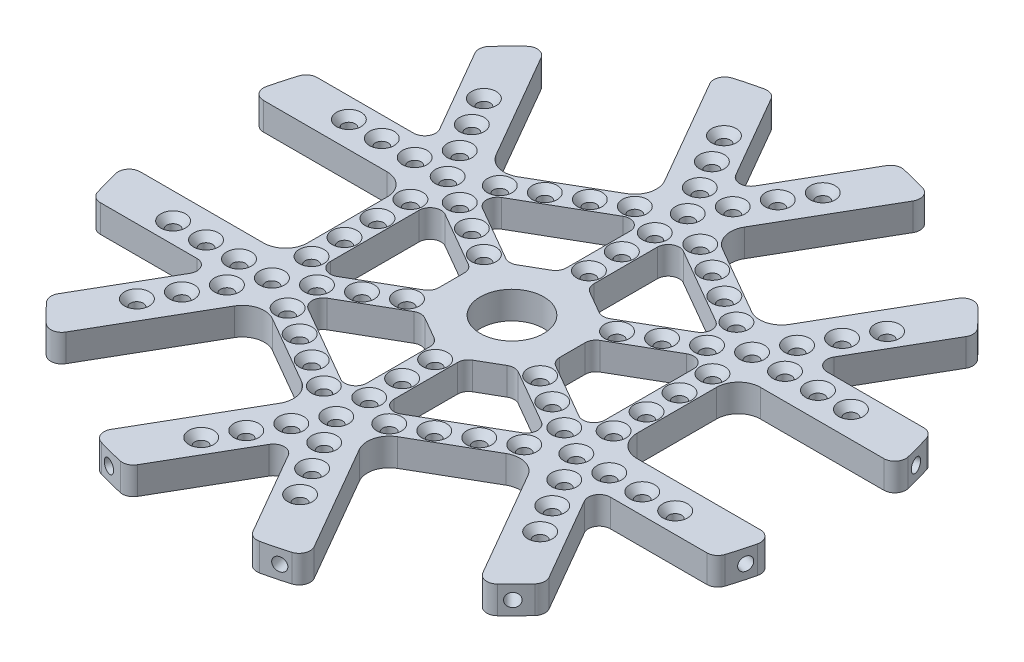
SolidWorks part; units mm, degrees
material "6061-T6 (SS)"
ref_plane "Front Plane" through (0, 0, 0) normal (0, 0, 1) x (1, 0, 0)
ref_plane "Top Plane" through (0, 0, 0) normal (0, 1, 0) x (1, 0, 0)
ref_plane "Right Plane" through (0, 0, 0) normal (1, 0, 0) x (0, 0, -1)
sketch "Sketch1" plane through (0, 0, 0) normal (0, 1, 0) x (1, 0, 0)
  line L0 (0, -76.2) -> (0, 94.2288) construction
  line L1 (0, 0) -> (-65.9911, 38.1) construction
  line L2 (0, 0) -> (-19.722, 73.6035) construction
  line L3 (-14.2714, 74.8516) -> (0, 50.1328)
  line L4 (-25.0664, 71.9591) -> (0, 28.5428)
  line L5 (0, 50.1328) -> (0, 34.0421)
  line L6 (0, 0) -> (-3.175, 0)
  line L7 (0, 0) -> (0, 34.0421)
  line L8 (0, 34.0421) -> (-3.175, 34.0421)
  line L9 (-3.175, 0) -> (-3.175, 34.0421)
  arc A1 (-25.0664, 71.9591) -> (-19.722, 73.6035) centre (0, 0) cw
  arc A3 (-14.2714, 74.8516) -> (-19.722, 73.6035) centre (0, 0) ccw
  circle A4 centre (0, 0) radius 76.2
  dimension "D6" = 152.4
  dimension "D7" = 76.2
  dimension "D8" = 76.2
  dimension "D1" = 15
  dimension "D2" = 60
  dimension "D3" = 30
  dimension "D4" = 10.795
  dimension "D5" = 3.175
extrude "Boss-Extrude1" add sketch "Sketch1" along normal blind 6.35 contours L3 A3 A1 L4 L8 L5
mirror "Mirror1" of "Boss-Extrude1"
sketch "Sketch2" plane through (0, 0, 0) normal (0, 0, 1) x (1, 0, 0)
  line L0 (0, 6.35) -> (0, 0)
  line L1 (3.175, 6.35) -> (-3.175, 6.35) construction
pattern_circular "CirPattern9" count 6 over 360 about axis through (0, 0, 0) along (0, 1, 0) of bodies 102
ref_plane "Plane1" through (3.175, 6.35, 0) normal (0, 0, -1) x (-1, 0, 0)
sketch "Sketch4" plane through (0, 6.35, 0) normal (0, 1, 0) x (1, 0, 0)
  line L1 (0, 16.1312) -> (-13.97, 8.0656)
  line L2 (-13.97, 8.0656) -> (-13.97, -8.0656)
  line L3 (-13.97, -8.0656) -> (0, -16.1312)
  line L4 (0, -16.1312) -> (13.97, -8.0656)
  line L5 (13.97, -8.0656) -> (13.97, 8.0656)
  line L6 (13.97, 8.0656) -> (0, 16.1312)
  circle A0 centre (0, 0) radius 13.97 construction
  dimension "D1" = 27.94
extrude "Boss-Extrude2" add sketch "Sketch4" against normal blind 6.35
sketch "Sketch5" plane through (0, 6.35, 0) normal (0, 1, 0) x (1, 0, 0)
  circle A0 centre (0, 0) radius 6.35
extrude "Cut-Extrude1" cut sketch "Sketch5" against normal blind 6.35
sketch "Sketch6" plane through (0, 6.35, 0) normal (0, 1, 0) x (1, 0, 0)
  line L0 (-28.7945, 20.0372) -> (-2.9555, 34.9554)
  line L1 (-28.7945, 20.0372) -> (-31.9695, 25.5365)
  line L2 (-2.9555, 34.9554) -> (-6.1305, 40.4547)
  line L3 (-31.9695, 25.5365) -> (-6.1305, 40.4547)
  point P0 (-15.875, 27.4963)
  dimension "D1" = 6.35
  dimension "D2" = 31.75
extrude "Boss-Extrude3" add sketch "Sketch6" against normal blind 6.35
pattern_circular "CirPattern10" count 6 every 60 about axis through (0, 0, 0) along (0, 1, 0) of "Boss-Extrude3"
ref_plane "Plane4" through (0, 3.175, 0) normal (0, 1, 0) x (1, 0, 0)
extrude "Cut-Extrude3" cut sketch "Sketch46" against normal blind 7.62
sketch "Sketch46" plane through (0, 6.35, 0) normal (0, 1, 0) x (1, 0, 0)
  line L0 (3.175, -34.8287) -> (3.5156, -34.632)
  line L2 (3.5156, -34.632) -> (3.175, -34.0421)
  line L4 (3.5156, -34.632) -> (3.175, -34.0421)
  line L5 (3.5156, -34.632) -> (3.175, -34.0421) construction
  line L6 (3.175, -34.0421) -> (3.175, -34.8287)
  line L7 (3.175, -34.0421) -> (3.5156, -34.632)
  line L8 (0, -3.4925) -> (0, 3.4925) construction
  line L9 (-3.5156, -34.632) -> (-3.175, -34.0421)
  line L10 (-3.175, -34.8287) -> (-3.5156, -34.632)
  line L11 (-3.175, -34.0421) -> (-3.175, -34.8287)
  line L12 (-31.0688, -14.2714) -> (-31.75, -14.6647)
  line L13 (-31.75, -14.2714) -> (-31.0688, -14.2714)
  line L14 (-31.75, -14.6647) -> (-31.75, -14.2714)
  line L15 (-28.2344, -20.3606) -> (-27.8938, -19.7707)
  line L16 (-27.8938, -19.7707) -> (-28.575, -20.164)
  line L17 (-28.575, -20.164) -> (-28.2344, -20.3606)
  line L18 (-27.8938, 19.7707) -> (-28.575, 20.164)
  line L19 (-28.2344, 20.3606) -> (-27.8938, 19.7707)
  line L20 (-28.575, 20.164) -> (-28.2344, 20.3606)
  line L21 (-31.75, 14.2714) -> (-31.0688, 14.2714)
  line L22 (-31.0688, 14.2714) -> (-31.75, 14.6647)
  line L23 (-31.75, 14.6647) -> (-31.75, 14.2714)
  line L24 (3.175, 34.0421) -> (3.175, 34.8287)
  line L25 (3.5156, 34.632) -> (3.175, 34.0421)
  line L26 (3.175, 34.8287) -> (3.5156, 34.632)
  line L27 (-3.5156, 34.632) -> (-3.175, 34.0421)
  line L28 (-3.175, 34.0421) -> (-3.175, 34.8287)
  line L29 (-3.175, 34.8287) -> (-3.5156, 34.632)
  line L30 (31.0688, 14.2714) -> (31.75, 14.6647)
  line L31 (31.75, 14.2714) -> (31.0688, 14.2714)
  line L32 (31.75, 14.6647) -> (31.75, 14.2714)
  line L33 (28.2344, 20.3606) -> (27.8938, 19.7707)
  line L34 (27.8938, 19.7707) -> (28.575, 20.164)
  line L35 (28.575, 20.164) -> (28.2344, 20.3606)
  line L36 (27.8938, -19.7707) -> (28.575, -20.164)
  line L37 (28.2344, -20.3606) -> (27.8938, -19.7707)
  line L38 (28.575, -20.164) -> (28.2344, -20.3606)
  line L39 (31.75, -14.2714) -> (31.0688, -14.2714)
  line L40 (31.0688, -14.2714) -> (31.75, -14.6647)
  line L41 (31.75, -14.6647) -> (31.75, -14.2714)
  point P44 (0, 0)
  dimension "D1" = 6
fillet "Fillet5" radius 2.54 54 edges at (10.795, 3.175, 9.8987) (0, 3.175, -50.1328) (43.4163, 3.175, 25.0664) (71.9591, 3.175, 25.0664) (74.8516, 3.175, 14.2714) (13.97, 3.175, 4.3994) (57.6877, 3.175, 49.7852) (-25.0664, 3.175, -71.9591) (49.7852, 3.175, 57.6877) (-14.2714, 3.175, -74.8516) (-3.175, 3.175, 14.2981) (0, 3.175, 50.1328) (14.2714, 3.175, 74.8516) (25.0664, 3.175, 71.9591) (3.175, 3.175, 14.2981) (-14.2714, 3.175, 74.8516) (-25.0664, 3.175, 71.9591) (-13.97, 3.175, 4.3994) (-43.4163, 3.175, 25.0664) (-57.6877, 3.175, 49.7852) (-49.7852, 3.175, 57.6877) (-10.795, 3.175, 9.8987) (-71.9591, 3.175, 25.0664) (-74.8516, 3.175, 14.2714) (-10.795, 3.175, -9.8987) (-43.4163, 3.175, -25.0664) (-71.9591, 3.175, -25.0664) (-74.8516, 3.175, -14.2714) (-13.97, 3.175, -4.3994) (-57.6877, 3.175, -49.7852) (-49.7852, 3.175, -57.6877) (14.2714, 3.175, -74.8516) (25.0664, 3.175, -71.9591) (-3.175, 3.175, 34.8287) (3.175, 3.175, 34.8287) (3.175, 3.175, -14.2981) (28.575, 3.175, 20.164) (-3.175, 3.175, -14.2981) (31.75, 3.175, 14.6647) (31.75, 3.175, -14.6647) (28.575, 3.175, -20.164) (3.175, 3.175, -34.8287) (-3.175, 3.175, -34.8287) (-28.575, 3.175, -20.164) (-31.75, 3.175, -14.6647) (-31.75, 3.175, 14.6647) (-28.575, 3.175, 20.164) (13.97, 3.175, -4.3994) (10.795, 3.175, -9.8987) (43.4163, 3.175, -25.0664) (57.6877, 3.175, -49.7852) (49.7852, 3.175, -57.6877) (71.9591, 3.175, -25.0664) (74.8516, 3.175, -14.2714)
fillet "Fillet6" radius 5.08 12 edges at (38.1, 3.175, 14.2714) (38.1, 3.175, -14.2714) (31.4094, 3.175, 25.8599) (6.6906, 3.175, 40.1313) (-6.6906, 3.175, 40.1313) (-31.4094, 3.175, 25.8599) (-38.1, 3.175, 14.2714) (-38.1, 3.175, -14.2714) (-31.4094, 3.175, -25.8599) (-6.6906, 3.175, -40.1313) (31.4094, 3.175, -25.8599) (6.6906, 3.175, -40.1313)
hole_wizard "CSK for #4 Flat Head Machine Screw1" positions "Sketch22" profile "Sketch23" countersink size "#4" standard "ANSI Inch"
sketch "Sketch22" plane through (0, 6.35, 0) normal (0, 1, 0) x (1, 0, 0)
  circle A0 centre (0, 0) radius 10.16
  point P2 (0, 17.78)
  point P4 (0, 25.4)
  point P6 (0, 33.02)
  point P8 (0, 40.64)
  dimension "D2" = 17.78
  dimension "D3" = 25.4
  dimension "D4" = 33.02
  dimension "D5" = 40.64
sketch "Sketch23" plane through (0, 6.35, -17.78) normal (1, 0, 0) x (0, 0, 1)
  line L0 (0, 0) -> (0, 8.5052)
  line L1 (0, 8.5052) -> (1.4732, 7.62)
  line L2 (1.4732, 7.62) -> (1.4732, 1.5925)
  line L3 (1.4732, 1.5925) -> (2.8575, 0)
  line L5 (2.8575, 0) -> (0, 0)
  line L6 (-1.4732, 1.5925) -> (-2.8575, 0) construction
  line L10 (0, 8.5052) -> (-1.4732, 7.62) construction
  line L11 (0, -6.35) -> (0, 107.95) construction
  dimension "Hole Dia." = 2.9464
  dimension "Hole Depth" = 7.62
  dimension "Near C'Sink Dia." = 5.715
  dimension "Near C'Sink Angle" = 82
  dimension "Drill Angle" = 118
pattern_circular "CirPattern11" count 6 every 60 about axis through (0, 0, 0) along (0, 1, 0) of "CSK for #4 Flat Head Machine Screw1"
hole_wizard "CSK for #4 Flat Head Machine Screw2" positions "Sketch25" profile "Sketch26" countersink size "#4" standard "ANSI Inch"
sketch "Sketch25" plane through (0, 6.35, 0) normal (0, 1, 0) x (1, 0, 0)
  line L0 (-19.0789, -73.7729) -> (-4.1148, -82.561) construction
  line L3 (19.0789, -73.7729) -> (0, -40.64)
  line L4 (0, -40.64) -> (-19.0789, -73.7729)
  line L5 (-35.1953, -20.32) -> (-77.4452, -20.32)
  arc A0 (-22.0333, -72.945) -> (-16.0935, -74.4811) centre (0, 0) ccw construction
  arc A1 (16.0935, -74.4811) -> (22.0333, -72.945) centre (0, 0) ccw construction
  point P25 (-42.8153, -20.32)
  point P27 (-50.4353, -20.32)
  point P32 (-58.0553, -20.32)
  dimension "D1" = 7.62
  dimension "D2" = 7.62
  dimension "D3" = 7.62
sketch "Sketch26" plane through (-58.0553, 6.35, 20.32) normal (1, 0, 0) x (0, 0, 1)
  line L0 (0, 0) -> (0, 8.5052)
  line L1 (0, 8.5052) -> (1.4732, 7.62)
  line L2 (1.4732, 7.62) -> (1.4732, 1.5925)
  line L3 (1.4732, 1.5925) -> (2.8575, 0)
  line L5 (2.8575, 0) -> (0, 0)
  line L6 (-1.4732, 1.5925) -> (-2.8575, 0) construction
  line L10 (0, 8.5052) -> (-1.4732, 7.62) construction
  line L11 (0, -6.35) -> (0, 107.95) construction
  dimension "Hole Dia." = 2.9464
  dimension "Hole Depth" = 7.62
  dimension "Near C'Sink Dia." = 5.715
  dimension "Near C'Sink Angle" = 82
  dimension "Drill Angle" = 118
sketch "Sketch27" plane through (0, 6.35, 0) normal (0, 1, 0) x (1, 0, 0)
  line L0 (0, 0) -> (0, -79.3578)
mirror "Mirror2" about plane through (0, 0, 0) normal (1, 0, 0) of "CSK for #4 Flat Head Machine Screw2"
pattern_circular "CirPattern12" count 6 over 360 about axis through (0, 0, 0) along (0, 1, 0) of "CSK for #4 Flat Head Machine Screw2", "Mirror2"
hole_wizard "CSK for #4 Flat Head Machine Screw3" positions "Sketch28" profile "Sketch29" countersink size "#4" standard "ANSI Inch"
sketch "Sketch28" plane through (0, 6.35, 0) normal (0, 1, 0) x (1, 0, 0)
  line L0 (3.2873, 38.43) -> (31.6799, 22.0375)
  line L3 (27.01, 28.3999) -> (11.09, 37.5913) construction
  line L4 (18.2785, 29.7748) -> (19.866, 32.5244)
  line L7 (18.2785, 29.7748) -> (16.691, 27.0252)
  line L8 (6.985, 32.629) -> (24.765, 22.3637) construction
  line L11 (0, 0) -> (0, 68.0291)
  line L12 (0, 68.0291) -> (0, 0)
  line L14 (0, 0) -> (40.501, 70.1499)
  point P0 (27.3612, 24.5309)
  point P2 (20.7621, 28.3409)
  point P4 (14.1629, 32.1509)
  point P6 (7.5638, 35.9609)
  dimension "D1" = 30
  dimension "D2" = 3.81
  dimension "D3" = 11.43
  dimension "D4" = 3.81
  dimension "D5" = 11.43
sketch "Sketch29" plane through (27.3612, 6.35, -24.5309) normal (1, 0, 0) x (0, 0, 1)
  line L0 (0, 0) -> (0, 8.5052)
  line L1 (0, 8.5052) -> (1.4732, 7.62)
  line L2 (1.4732, 7.62) -> (1.4732, 1.5925)
  line L3 (1.4732, 1.5925) -> (2.8575, 0)
  line L5 (2.8575, 0) -> (0, 0)
  line L6 (-1.4732, 1.5925) -> (-2.8575, 0) construction
  line L10 (0, 8.5052) -> (-1.4732, 7.62) construction
  line L11 (0, -6.35) -> (0, 107.95) construction
  dimension "Hole Dia." = 2.9464
  dimension "Hole Depth" = 7.62
  dimension "Near C'Sink Dia." = 5.715
  dimension "Near C'Sink Angle" = 82
  dimension "Drill Angle" = 118
pattern_circular "CirPattern13" count 6 over 360 about axis through (0, 0, 0) along (0, 1, 0) of "CSK for #4 Flat Head Machine Screw3"
sketch "Sketch30" plane through (0, 6.35, 0) normal (0, 1, 0) x (1, 0, 0)
  circle A0 centre (0, 0) radius 6.35
extrude "Boss-Extrude4" add sketch "Sketch30" against normal blind 6.35
hole_wizard "9/16 Clearance Hole1" positions "Sketch33" profile "Sketch35" hole size "9/16" standard "ANSI Inch" end condition through all
sketch "Sketch33" plane through (0, 6.35, 0) normal (0, 1, 0) x (1, 0, 0)
  point P0 (0, 0)
sketch "Sketch35" plane through (0, 6.35, 0) normal (1, 0, 0) x (0, 0, 1)
  line L0 (0, 0) -> (0, 6.35)
  line L1 (0, 6.35) -> (7.3419, 6.35)
  line L2 (7.3419, 6.35) -> (7.3419, 0)
  line L5 (7.3419, 0) -> (0, 0)
  line L11 (0, -6.35) -> (0, 107.95) construction
  dimension "Thru Hole Dia." = 14.6837
  dimension "Thru Hole Depth" = 6.35
ref_plane "Plane5" through (-19.0634, 0, -73.7131) normal (-0.2504, 0, -0.9681) x (-0.9681, 0, 0.2504)
sketch "Sketch41" plane through (0, 6.35, 0) normal (0, 1, 0) x (1, 0, 0)
  circle A0 centre (0, 0) radius 76.2
sketch "Sketch43" plane through (0, 6.35, 0) normal (0, 1, 0) x (1, 0, 0)
  circle A0 centre (73.79, -18.7251) radius 0.0712
ref_plane "Plane7" through (19.722, 0, -73.6035) normal (0.2588, 0, -0.9659) x (0, -1, 0)
hole_wizard "Tapped Hole for #4-40 Helicoil2" positions "Sketch50" profile "Sketch51" tap size "#4-40" standard "Helicoil® Inch"
sketch "Sketch50" plane through (19.722, 0, -73.6035) normal (0.2588, 0, -0.9659) x (0, -1, 0)
  line L0 (0, -2.403) -> (0, 3.732) construction
  line L1 (-6.35, -2.403) -> (0, -2.403) construction
  point P0 (-3.175, 0.137)
  dimension "D1" = 3.175
  dimension "D2" = 2.54
sketch "Sketch51" plane through (19.5896, 3.175, -73.639) normal (0, 1, 0) x (-0.9659, 0, -0.2588)
  line L0 (0, 0) -> (0, 10.8217)
  line L1 (0, 10.8217) -> (1.524, 9.906)
  line L2 (1.524, 9.906) -> (1.524, 0)
  line L5 (1.524, 0) -> (0, 0)
  line L10 (0, 10.8217) -> (-1.524, 9.906) construction
  line L11 (0, -6.35) -> (0, 107.95) construction
  dimension "Tap Drill Dia." = 3.048
  dimension "Tap Drill Depth" = 9.906
  dimension "Drill Angle" = 118
pattern_circular "CirPattern14" count 12 over 360 about axis through (0, 6.35, 0) along (0, 1, 0) of "Tapped Hole for #4-40 Helicoil2"
equation "\"anchor\"= .425"
equation "\"D4@Sketch1\"=\"anchor\""
equation "\"half arm\"= .125"
equation "\"D5@Sketch1\"=\"half arm\""
equation "\"strut\"= .25"
equation "\"D1@Sketch6\"=\"strut\""
